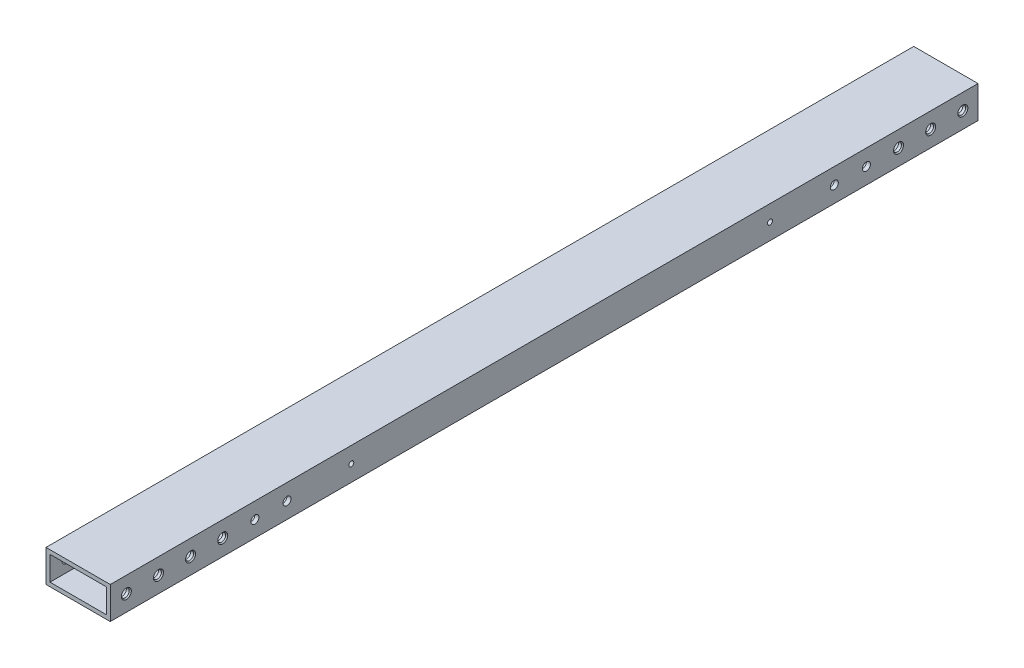
SolidWorks part; units mm, degrees
material "6061 Alloy"
ref_plane "Front Plane" through (0, 0, 0) normal (0, 0, 1) x (1, 0, 0)
ref_plane "Top Plane" through (0, 0, 0) normal (0, 1, 0) x (1, 0, 0)
ref_plane "Right Plane" through (0, 0, 0) normal (1, 0, 0) x (0, 0, -1)
sketch "Sketch1" plane through (0, 0, 0) normal (0, 0, 1) x (1, 0, 0)
  line L0 (-22.225, 9.525) -> (22.225, 9.525)
  line L2 (-25.4, 12.7) -> (25.4, 12.7)
  line L3 (-25.4, 12.7) -> (-25.4, -12.7)
  line L4 (-25.4, -12.7) -> (25.4, -12.7)
  line L5 (25.4, 12.7) -> (25.4, -12.7)
  line L10 (22.225, 9.525) -> (22.225, -9.525)
  line L11 (-22.225, -9.525) -> (22.225, -9.525)
  line L12 (-22.225, 9.525) -> (-22.225, -9.525)
  point P12 (0, 12.7)
  point P14 (25.4, 0)
  dimension "Wall Thickness" = 3.175
  dimension "Outside Width" = 50.8
  dimension "Outside Height" = 25.4
  dimension "Inside Height" = 19.05
  dimension "Inside Width" = 44.45
sketch "Sketch2" plane through (0, 0, 0) normal (1, 0, 0) x (0, 0, -1)
  line L0 (342.9, 0) -> (-342.9, 0)
  point P4 (0, 0)
  point P7 (-342.9, 0)
  point P10 (342.9, 0)
  dimension "Length" = 685.8
sketch "Sketch3" plane through (0, 0, 0) normal (0, 0, 1) x (1, 0, 0)
  line L21 (25.4, 12.7) -> (-25.4, 12.7)
  line L22 (25.4, -12.7) -> (25.4, 12.7)
  line L23 (-25.4, -12.7) -> (25.4, -12.7)
  line L24 (-25.4, 12.7) -> (-25.4, -12.7)
  line L25 (25.4, 12.7) -> (-25.4, 12.7)
  line L26 (25.4, -12.7) -> (25.4, 12.7)
  line L27 (-25.4, -12.7) -> (25.4, -12.7)
  line L28 (-25.4, 12.7) -> (-25.4, -12.7)
  line L29 (22.225, 9.525) -> (-22.225, 9.525)
  line L30 (22.225, -9.525) -> (22.225, 9.525)
  line L31 (-22.225, -9.525) -> (22.225, -9.525)
  line L32 (-22.225, 9.525) -> (-22.225, -9.525)
  line L33 (22.225, 9.525) -> (-22.225, 9.525)
  line L34 (22.225, -9.525) -> (22.225, 9.525)
  line L35 (-22.225, -9.525) -> (22.225, -9.525)
  line L36 (-22.225, 9.525) -> (-22.225, -9.525)
  dimension "D1" = 0
  dimension "D2" = 0
extrude "Boss-Extrude1" add sketch "Sketch3" along normal up to vertex (342.9 mm away) and the other way up to vertex (342.9 mm away) up to point (0, 0, 342.9) other way up to point (0, 0, -342.9)
sketch "Drawing Reference" plane through (0, 0, 0) normal (1, 0, 0) x (0, 0, -1)
  line L0 (-342.9, 0) -> (342.9, 0) construction
  line L1 (0, -12.7) -> (0, 12.7) construction
  line L2 (-342.9, -12.7) -> (342.9, -12.7) construction
  line L5 (-342.9, 12.7) -> (342.9, 12.7) construction
  point P7 (-306.324, 0)
  point P8 (306.324, 0)
  dimension "D1" = 36.576
sketch "Sketch5" plane through (25.4, 0, 0) normal (1, 0, 0) x (0, 0, -1)
  line L0 (-342.9, 0) -> (-279.4, 0)
  line L1 (-342.9, -12.7) -> (-342.9, 12.7) construction
  line L2 (-279.4, 0) -> (-254, 0)
  line L3 (-254, 0) -> (-228.6, 0)
  line L4 (-228.6, 0) -> (-203.2, 0)
sketch "Sketch8" plane through (25.4, 0, 0) normal (1, 0, 0) x (0, 0, -1)
  line L0 (342.9, 0) -> (305.5118, 0)
  line L1 (342.9, -12.7) -> (342.9, 12.7) construction
  line L2 (305.5118, 0) -> (280.1118, 0)
  line L3 (280.1118, 0) -> (254.7118, 0)
  line L4 (254.7118, 0) -> (229.3118, 0)
hole_wizard "1/4 (0.25) Diameter Hole3" positions "Sketch12" profile "Sketch13" hole size "1/4" standard "ANSI Inch" end condition through all
sketch "Sketch12" plane through (-25.4, 0, 0) normal (-1, 0, 0) x (0, 0, 1)
  point P0 (-330.9118, 0)
sketch "Sketch13" plane through (-25.4, 0, -330.9118) normal (0, 1, 0) x (0, 0, 1)
  line L0 (0, 0) -> (0, 50.8)
  line L1 (0, 50.8) -> (3.9624, 50.8)
  line L2 (3.175, 49.8942) -> (3.175, 0)
  line L5 (3.175, 0) -> (0, 0)
  line L7 (3.9624, 50.8) -> (3.175, 49.8942)
  line L8 (-3.9624, 50.8) -> (-3.175, 49.8942) construction
  line L11 (0, -6.35) -> (0, 107.95) construction
  dimension "Thru Hole Dia." = 6.35
  dimension "Thru Hole Depth" = 50.8
  dimension "Far C'Sink Dia." = 7.9248
  dimension "Far C'Sink Angle" = 82
hole_wizard "1/4 (0.25) Diameter Hole4" positions "Sketch14" profile "Sketch15" hole size "1/4" standard "ANSI Inch" end condition through all
sketch "Sketch14" plane through (-25.4, 0, 0) normal (-1, 0, 0) x (0, 0, 1)
  point P0 (304.8, 0)
  point P3 (330.2, 0)
sketch "Sketch15" plane through (-25.4, 0, 304.8) normal (0, 1, 0) x (0, 0, 1)
  line L0 (0, 0) -> (0, 50.8)
  line L1 (0, 50.8) -> (3.9624, 50.8)
  line L2 (3.175, 49.8942) -> (3.175, 0)
  line L5 (3.175, 0) -> (0, 0)
  line L7 (3.9624, 50.8) -> (3.175, 49.8942)
  line L8 (-3.9624, 50.8) -> (-3.175, 49.8942) construction
  line L11 (0, -6.35) -> (0, 107.95) construction
  dimension "Thru Hole Dia." = 6.35
  dimension "Thru Hole Depth" = 50.8
  dimension "Far C'Sink Dia." = 7.9248
  dimension "Far C'Sink Angle" = 82
hole_wizard "1/4 (0.25) Diameter Hole5" positions "Sketch17" profile "Sketch18" hole size "1/4" standard "ANSI Inch" end condition through all
sketch "Sketch17" plane through (25.4, 0, 0) normal (1, 0, 0) x (0, 0, -1)
  point P0 (305.5118, 0)
  point P3 (280.1118, 0)
sketch "Sketch18" plane through (25.4, 0, -305.5118) normal (0, 1, 0) x (0, 0, -1)
  line L0 (0, 0) -> (0, 50.8)
  line L1 (0, 50.8) -> (3.175, 50.8)
  line L2 (3.175, 50.8) -> (3.175, 0.9058)
  line L3 (3.175, 0.9058) -> (3.9624, 0)
  line L5 (3.9624, 0) -> (0, 0)
  line L6 (-3.175, 0.9058) -> (-3.9624, 0) construction
  line L11 (0, -6.35) -> (0, 107.95) construction
  dimension "Thru Hole Dia." = 6.35
  dimension "Thru Hole Depth" = 50.8
  dimension "Near C'Sink Dia." = 7.9248
  dimension "Near C'Sink Angle" = 82
hole_wizard "1/4 (0.25) Diameter Hole6" positions "Sketch19" profile "Sketch20" hole size "1/4" standard "ANSI Inch" end condition through all
sketch "Sketch19" plane through (25.4, 0, 0) normal (1, 0, 0) x (0, 0, -1)
  point P0 (229.3118, 0)
  point P3 (254.7118, 0)
sketch "Sketch20" plane through (25.4, 0, -229.3118) normal (0, 1, 0) x (0, 0, -1)
  line L0 (0, 0) -> (0, 50.8)
  line L1 (0, 50.8) -> (3.175, 50.8)
  line L2 (3.175, 50.8) -> (3.175, 0)
  line L5 (3.175, 0) -> (0, 0)
  line L11 (0, -6.35) -> (0, 107.95) construction
  dimension "Thru Hole Dia." = 6.35
  dimension "Thru Hole Depth" = 50.8
hole_wizard "1/4 (0.25) Diameter Hole7" positions "Sketch21" profile "Sketch22" hole size "1/4" standard "ANSI Inch" end condition through all
sketch "Sketch21" plane through (25.4, 0, 0) normal (1, 0, 0) x (0, 0, -1)
  point P0 (-203.2, 0)
  point P3 (-228.6, 0)
sketch "Sketch22" plane through (25.4, 0, 203.2) normal (0, 1, 0) x (0, 0, -1)
  line L0 (0, 0) -> (0, 50.8)
  line L1 (0, 50.8) -> (3.175, 50.8)
  line L2 (3.175, 50.8) -> (3.175, 0)
  line L5 (3.175, 0) -> (0, 0)
  line L11 (0, -6.35) -> (0, 107.95) construction
  dimension "Thru Hole Dia." = 6.35
  dimension "Thru Hole Depth" = 50.8
hole_wizard "1/4 (0.25) Diameter Hole8" positions "Sketch23" profile "Sketch24" hole size "1/4" standard "ANSI Inch" end condition through all
sketch "Sketch23" plane through (25.4, 0, 0) normal (1, 0, 0) x (0, 0, -1)
  point P0 (-279.4, 0)
  point P3 (-254, 0)
sketch "Sketch24" plane through (25.4, 0, 279.4) normal (0, 1, 0) x (0, 0, -1)
  line L0 (0, 0) -> (0, 50.8)
  line L1 (0, 50.8) -> (3.175, 50.8)
  line L2 (3.175, 50.8) -> (3.175, 0.9058)
  line L3 (3.175, 0.9058) -> (3.9624, 0)
  line L5 (3.9624, 0) -> (0, 0)
  line L6 (-3.175, 0.9058) -> (-3.9624, 0) construction
  line L11 (0, -6.35) -> (0, 107.95) construction
  dimension "Thru Hole Dia." = 6.35
  dimension "Thru Hole Depth" = 50.8
  dimension "Near C'Sink Dia." = 7.9248
  dimension "Near C'Sink Angle" = 82
sketch "Sketch25" plane through (25.4, 0, 0) normal (1, 0, 0) x (0, 0, -1)
  line L0 (-203.2, 0) -> (-152.4, 0)
  line L1 (229.3118, 0) -> (178.5118, 0)
hole_wizard "5/32 (0.15625) Diameter Hole1" positions "Sketch26" profile "Sketch27" hole size "5/32" standard "ANSI Inch" end condition through all
sketch "Sketch26" plane through (25.4, 0, 0) normal (1, 0, 0) x (0, 0, -1)
  point P0 (-152.4, 0)
  point P3 (178.5118, 0)
sketch "Sketch27" plane through (25.4, 0, 152.4) normal (0, 1, 0) x (0, 0, -1)
  line L0 (0, 0) -> (0, 50.8)
  line L1 (0, 50.8) -> (1.9844, 50.8)
  line L2 (1.9844, 50.8) -> (1.9844, 0)
  line L5 (1.9844, 0) -> (0, 0)
  line L11 (0, -6.35) -> (0, 107.95) construction
  dimension "Thru Hole Dia." = 3.9688
  dimension "Thru Hole Depth" = 50.8
sketch "Sketch28" plane through (-25.4, 0, 0) normal (-1, 0, 0) x (0, 0, 1)
  line L0 (102.8316, 0) -> (77.4316, 0)
  line L1 (-103.5434, 0) -> (-128.9434, 0)
hole_wizard "1/2 (0.5) Diameter Hole1" positions "Sketch29" profile "Sketch30" hole size "1/2" standard "ANSI Inch"
sketch "Sketch29" plane through (-25.4, 0, 0) normal (-1, 0, 0) x (0, 0, 1)
  point P1 (-591.3016, -480.8022)
  point P3 (-103.5434, 0)
  point P6 (77.4316, 0)
  point P9 (102.8316, 0)
  point P13 (-128.9434, 0)
sketch "Sketch30" plane through (-25.4, -480.8022, -591.3016) normal (0, 1, 0) x (0, 0, 1)
  line L0 (0, 0) -> (0, 10.1655)
  line L1 (0, 10.1655) -> (6.35, 6.35)
  line L2 (6.35, 6.35) -> (6.35, 0)
  line L5 (6.35, 0) -> (0, 0)
  line L10 (0, 10.1655) -> (-6.35, 6.35) construction
  line L11 (0, -6.35) -> (0, 107.95) construction
  dimension "Hole Dia." = 12.7
  dimension "Hole Depth" = 6.35
  dimension "Drill Angle" = 118
equation "\"D1@Drawing Reference\"=\"Outside Width@Sketch1\" * 0.72"
